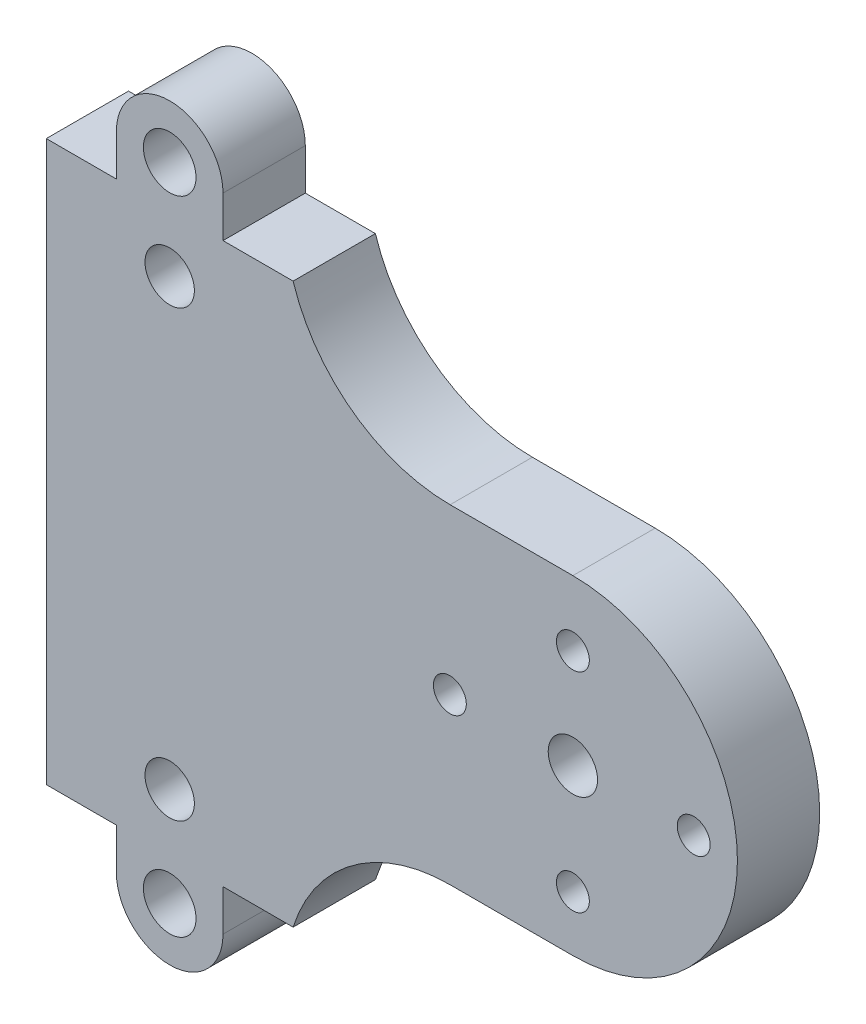
SolidWorks part; units mm, degrees
ref_plane "Plan de face" through (0, 0, 0) normal (0, 0, 1) x (1, 0, 0)
ref_plane "Plan de dessus" through (0, 0, 0) normal (0, 1, 0) x (1, 0, 0)
ref_plane "Plan de droite" through (0, 0, 0) normal (1, 0, 0) x (0, 0, -1)
sketch "Esquisse1" plane through (0, 0, 0) normal (0, 0, 1) x (1, 0, 0)
  line L0 (-13.5846, -30.0471) -> (-13.5846, -25.5471)
  line L1 (-13.8346, -25.2971) -> (-16.3346, -25.2971)
  line L2 (-16.5846, -25.0471) -> (-16.5846, 6.4529)
  line L3 (-16.3346, 6.7029) -> (-13.8346, 6.7029)
  line L4 (-13.5846, 6.9529) -> (-13.5846, 11.4529)
  line L5 (-13.3346, 11.7029) -> (-8.5846, 11.7029)
  line L6 (-8.5846, 11.7029) -> (-8.5846, 6.7029)
  line L7 (-8.5846, 6.7029) -> (-7.4918, 6.7029)
  line L8 (-7.4918, 6.7029) -> (-4.0345, 6.7029)
  line L9 (-4.0345, -25.2971) -> (-7.4918, -25.2971)
  line L10 (-7.4918, -25.2971) -> (-8.5846, -25.2971)
  line L11 (-8.5846, -25.2971) -> (-8.5846, -30.2971)
  line L12 (-8.5846, -30.2971) -> (-13.3346, -30.2971)
  line L13 (-13.3346, -30.2971) -> (-13.5846, -30.2971)
  line L14 (-13.5846, -30.2971) -> (-13.5846, -30.0471)
  line L15 (-13.5846, -25.5471) -> (-13.5846, -25.2971)
  line L16 (-13.5846, -25.2971) -> (-13.8346, -25.2971)
  line L17 (-16.3346, -25.2971) -> (-16.5846, -25.2971)
  line L18 (-16.5846, -25.2971) -> (-16.5846, -25.0471)
  line L19 (-16.3346, 6.7029) -> (-16.5846, 6.7029)
  line L20 (-16.5846, 6.7029) -> (-16.5846, 6.4529)
  line L21 (-13.5846, 6.9529) -> (-13.5846, 6.7029)
  line L22 (-13.5846, 6.7029) -> (-13.8346, 6.7029)
  line L23 (-13.5846, 11.4529) -> (-13.5846, 11.7029)
  line L24 (-13.5846, 11.7029) -> (-13.3346, 11.7029)
  arc A0 (3.4488, 4.7029) -> (-4.0345, 6.7029) centre (-4.0345, -8.2971) ccw
  arc A1 (3.4488, 4.7029) -> (18.4154, 0.7029) centre (18.4154, 30.7029) ccw
  arc A2 (18.4154, -19.2971) -> (18.4154, 0.7029) centre (18.4154, -9.2971) ccw
  arc A3 (18.4154, -19.2971) -> (3.4488, -23.2971) centre (18.4154, -49.2971) ccw
  arc A4 (-4.0345, -25.2971) -> (3.4488, -23.2971) centre (-4.0345, -10.2971) ccw
  circle A5 centre (18.4779, -2.2971) radius 1
  circle A6 centre (25.4154, -9.3596) radius 1
  circle A7 centre (18.4154, -9.2971) radius 1.5
  circle A8 centre (11.4154, -9.2347) radius 1
  circle A9 centre (18.3529, -16.2971) radius 1
extrude "Boss.-Extru.1" add sketch "Esquisse1" along normal blind 5
sketch "Esquisse2" plane through (0, 0, 0) normal (0, 0, -1) x (-1, 0, 0)
  line L0 (-18.4154, -9.2971) -> (7.3764, -9.2971) construction
  line L2 (1.5846, -19.2971) -> (1.5846, -26.2971) construction
  line L3 (4.0345, 6.7029) -> (8.5846, 6.7029) construction
  line L4 (1.5846, -19.2971) -> (1.5846, -25.2971)
  line L5 (-26.8332, -33.657) -> (-26.1987, -19.2971)
  line L6 (21.5846, -33.657) -> (-26.8332, -33.657)
  line L7 (21.5846, 7.7029) -> (1.5846, 7.7029)
  line L8 (21.5846, -26.2971) -> (21.5846, -33.657)
  line L9 (1.5846, 6.7029) -> (1.5846, 7.7029)
  line L10 (-26.1987, -19.2971) -> (1.5846, -19.2971)
  line L11 (1.5846, -25.2971) -> (1.5846, -26.2971)
  line L12 (-26.1987, 0.7029) -> (1.5846, 0.7029)
  line L13 (21.5846, -26.2971) -> (1.5846, -26.2971)
  line L15 (21.5846, 7.7029) -> (21.5846, 15.0627)
  line L16 (21.5846, 15.0627) -> (-26.8332, 15.0627)
  line L17 (-26.8332, 15.0627) -> (-26.1987, 0.7029)
  line L18 (1.5846, 0.7029) -> (1.5846, 7.7029) construction
  line L19 (1.5846, 0.7029) -> (1.5846, 6.7029)
  arc A1 (-18.4154, 0.7029) -> (-18.4154, -19.2971) centre (-18.4154, -9.2971) ccw construction
extrude "Enlèv. mat.-Extru.1" cut sketch "Esquisse2" against normal blind 5
sketch "Esquisse3" plane through (0, 0, 0) normal (0, 0, -1) x (-1, 0, 0)
  line L0 (8.5846, 7.7029) -> (13.5846, 7.7029) construction
  line L1 (21.5846, -26.2971) -> (1.5846, -26.2971)
  line L2 (21.5846, -26.2971) -> (21.5846, 7.7029)
  line L3 (21.5846, 7.7029) -> (1.5846, 7.7029)
  line L4 (1.5846, -26.2971) -> (1.5846, 7.7029)
  line L5 (13.5846, -26.2971) -> (8.5846, -26.2971) construction
  dimension "D1" = 0
  dimension "D2" = 20
  dimension "D3" = 0
extrude "Boss.-Extru.2" add sketch "Esquisse3" against normal blind 5
sketch "Esquisse4" plane through (0, 0, 0) normal (0, 0, -1) x (-1, 0, 0)
  line L1 (21.5846, -26.2971) -> (1.5846, -26.2971) construction
  line L2 (1.5846, -26.2971) -> (1.5846, -19.2971) construction
  line L4 (28.8831, -28.9494) -> (19.0846, -28.9494)
  line L5 (28.8831, -28.9494) -> (28.8831, 10.9087)
  line L6 (28.8831, 10.9087) -> (19.0846, 10.9087)
  line L7 (19.0846, -28.9494) -> (19.0846, 10.9087)
  circle A0 centre (9.0846, -22.7971) radius 1.5
  circle A1 centre (9.0846, 4.2029) radius 1.5
  dimension "D1" = 7.5
  dimension "D4" = 3
  dimension "D5" = 3
  dimension "D6" = 10
  dimension "D2" = 27
  dimension "D3" = 3.5
extrude "Enlèv. mat.-Extru.2" cut sketch "Esquisse4" against normal blind 5
sketch "Esquisse5" plane through (0, 0, 0) normal (0, 0, -1) x (-1, 0, 0)
  line L1 (1.5846, -26.2971) -> (-0.9154, -26.2971)
  line L2 (1.5846, -26.2971) -> (1.5846, 7.7029)
  line L3 (1.5846, 7.7029) -> (-0.9154, 7.7029)
  line L4 (-0.9154, -26.2971) -> (-0.9154, 7.7029)
  circle A0 centre (9.0846, -22.7971) radius 1.5 construction
  dimension "D1" = 10
extrude "Boss.-Extru.3" add sketch "Esquisse5" against normal up to vertex (5 mm away)
sketch "Esquisse6" plane through (0, 0, 0) normal (0, 0, -1) x (-1, 0, 0)
  line L0 (19.0846, -26.2971) -> (-0.9154, -26.2971) construction
  line L1 (-0.9154, 7.7029) -> (19.0846, 7.7029) construction
  line L2 (12.3246, -25.1248) -> (5.8446, -25.1248)
  line L4 (12.3246, -28.7971) -> (12.3246, -25.1248)
  line L6 (5.8446, -28.7971) -> (5.8446, -25.1248)
  line L7 (12.3246, 6.7577) -> (5.8446, 6.7577)
  line L8 (5.8446, 6.7577) -> (5.8446, 10.2029)
  line L9 (12.3246, 6.7577) -> (12.3246, 10.2029)
  circle A0 centre (9.0846, -28.7971) radius 1.6
  circle A1 centre (9.0846, 10.2029) radius 1.6
  arc A2 (5.8446, -28.7971) -> (12.3246, -28.7971) centre (9.0846, -28.7971) ccw
  arc A3 (12.3246, 10.2029) -> (5.8446, 10.2029) centre (9.0846, 10.2029) ccw
  circle A5 centre (9.0846, -22.7971) radius 1.5 construction
  dimension "D1" = 3.2
  dimension "D2" = 3.2
  dimension "D3" = 2.5
  dimension "D4" = 2.5
  dimension "D5" = 0
  dimension "D6" = 6.48
  dimension "D7" = 6.48
extrude "Boss.-Extru.4" add sketch "Esquisse6" against normal up to vertex (5 mm away)
sketch "Esquisse8" plane through (0, 0, 0) normal (0, 0, -1) x (-1, 0, 0)
  line L1 (1.5846, -38.4608) -> (-41.547, -38.4608)
  line L2 (1.5846, -38.4608) -> (1.5846, 10.3249)
  line L3 (1.5846, 10.3249) -> (-41.547, 10.3249)
  line L4 (-41.547, -38.4608) -> (-41.547, 10.3249)
  line L5 (11.5846, -22.4929) -> (6.5846, -22.4929) construction
  line L9 (29.789, -39.0457) -> (16.5846, -39.0457)
  line L10 (29.789, -39.0457) -> (29.789, 8.4016)
  line L11 (29.789, 8.4016) -> (16.5846, 8.4016)
  line L12 (16.5846, -39.0457) -> (16.5846, 8.4016)
  circle A1 centre (9.0846, -22.7971) radius 1.5 construction
  dimension "D1" = 5
  dimension "D2" = 2.5
  dimension "D3" = 2.5
  dimension "D4" = 5
extrude "Enlèv. mat.-Extru.3" cut sketch "Esquisse8" against normal blind 10
sketch "Esquisse9" plane through (0, 0, 0) normal (0, 0, -1) x (-1, 0, 0)
  line L11 (1.5846, -26.2971) -> (1.5846, 7.7029) construction
  line L12 (16.5846, 7.7029) -> (16.5846, -26.2971) construction
  line L14 (-15.4154, -19.2971) -> (1.5846, -19.2971)
  line L16 (-15.4154, 0.7029) -> (1.5846, 0.7029)
  line L17 (1.5846, -19.2971) -> (1.5846, 0.7029)
  circle A16 centre (-15.4154, -9.2971) radius 1.5
  arc A17 (-15.4154, 0.7029) -> (-15.4154, -19.2971) centre (-15.4154, -9.2971) ccw
  circle A19 centre (-15.4154, -15.9342) radius 1
  circle A20 centre (-22.7581, -9.2971) radius 1
  circle A21 centre (-15.4154, -3.2557) radius 1
  circle A22 centre (-7.9385, -9.2971) radius 1
  point P53 (16.5846, -9.2971)
  point P63 (0, 0)
  point P64 (0, 0)
  point P65 (0, 0)
  point P66 (0, 0)
  dimension "D1" = 20
  dimension "D2" = 2
  dimension "D3" = 3
  dimension "D4" = 2
  dimension "D5" = 2
  dimension "D6" = 2
extrude "Boss.-Extru.5" add sketch "Esquisse9" against normal up to vertex (5 mm away) up to point (-1.5846, -26.2971, 5)
fillet "Congé1" radius 10 2 edges at (-1.5846, 0.7029, 2.5) (-1.5846, -19.2971, 2.5)
